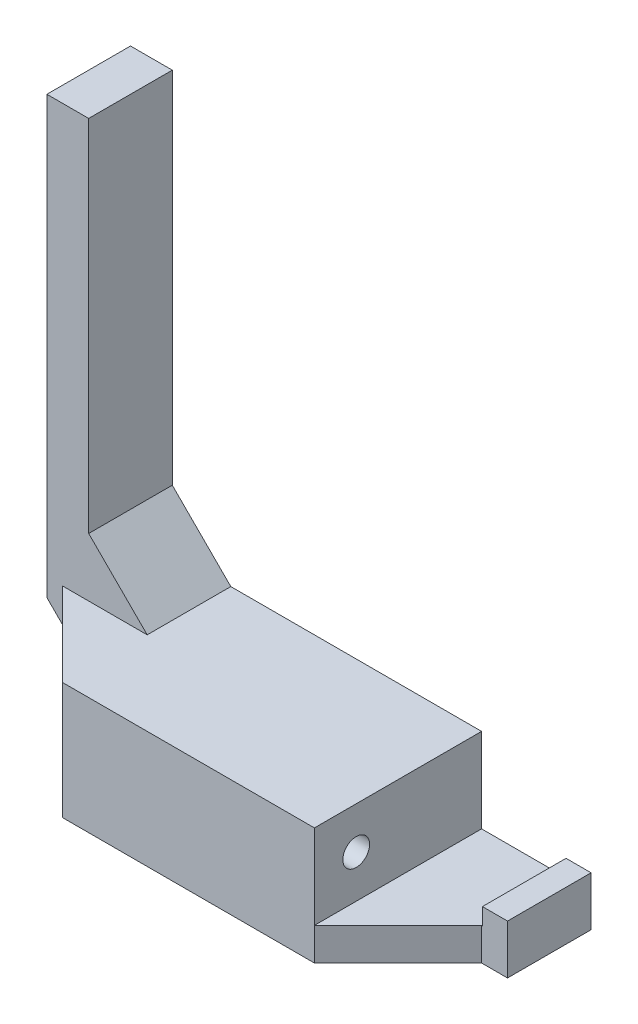
SolidWorks part; units mm, degrees
ref_plane "Front Plane" through (0, 0, 0) normal (0, 0, 1) x (1, 0, 0)
ref_plane "Top Plane" through (0, 0, 0) normal (0, 1, 0) x (1, 0, 0)
ref_plane "Right Plane" through (0, 0, 0) normal (1, 0, 0) x (0, 0, -1)
sketch "ｽｹｯﾁ1" plane through (0, 0, 0) normal (0, 0, 1) x (1, 0, 0)
  line L0 (0, 0) -> (0, 10.1)
  line L1 (0, 10.1) -> (-30, 10.1)
  line L2 (-30, 10.1) -> (-37, 17.1)
  line L3 (-37, 17.1) -> (-37, 60.1)
  line L4 (-37, 60.1) -> (-42, 60.1)
  line L5 (-42, 60.1) -> (-42, 7.9579)
  line L6 (-42, 7.9579) -> (-30.1421, -3.9)
  line L7 (-30.1421, -3.9) -> (13.1, -3.9)
  line L8 (13.1, -3.9) -> (13.1, 2)
  line L9 (13.1, 2) -> (10.1, 2)
  line L10 (10.1, 2) -> (10.1, 0)
  line L11 (10.1, 0) -> (0, 0)
  dimension "D1" = 5
  dimension "D2" = 10
  dimension "D3" = 14
  dimension "D4" = 3.9
  dimension "D5" = 2
  dimension "D6" = 3
  dimension "D7" = 10.1
  dimension "D8" = 135
  dimension "D9" = 50
  dimension "D10" = 37
  dimension "D11" = 30
extrude "ﾎﾞｽ - 押し出し1" add sketch "ｽｹｯﾁ1" along normal blind 10
sketch "ｽｹｯﾁ2" plane through (0, 0, 10) normal (0, 0, 1) x (1, 0, 0)
  line L1 (0, 10.1) -> (-30.1421, 10.1)
  line L2 (0, 10.1) -> (0, -3.9)
  line L3 (0, -3.9) -> (-30.1421, -3.9)
  line L4 (-30.1421, 10.1) -> (-30.1421, -3.9)
extrude "ﾎﾞｽ - 押し出し2" add sketch "ｽｹｯﾁ2" along normal blind 10
chamfer "面取り2" distance 10 angle 45 2 edges at (-30.1421, 3.1, 10) (0, -1.95, 10)
sketch "ｽｹｯﾁ3" plane through (0, 0, 0) normal (1, 0, 0) x (0, 0, -1)
  line L0 (-20, 10.1) -> (0, 10.1) construction
  line L1 (-20, 0) -> (-20, 10.1) construction
  circle A0 centre (-15, 5.1) radius 1.6
  dimension "D1" = 3.2
  dimension "D2" = 5
  dimension "D3" = 5
extrude "ｶｯﾄ - 押し出し1" cut sketch "ｽｹｯﾁ3" against normal through all
sketch "ｽｹｯﾁ4" plane through (-42, 0, 0) normal (-1, 0, 0) x (0, 0, 1)
  circle A0 centre (15, 5.1) radius 3
  dimension "D1" = 6
extrude "ｶｯﾄ - 押し出し2" cut sketch "ｽｹｯﾁ4" against normal blind 23
